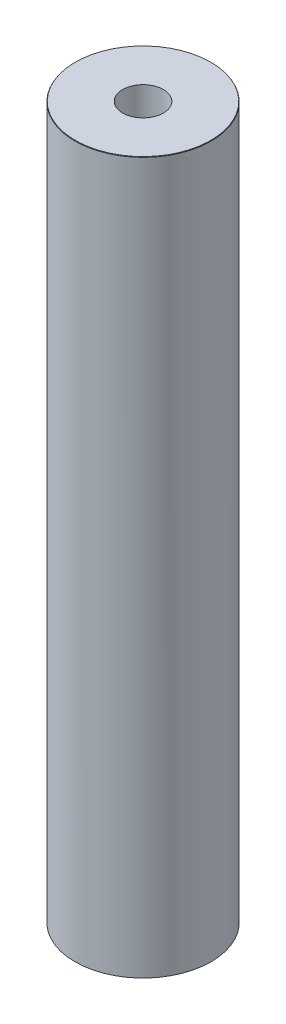
SolidWorks part; units mm, degrees
ref_plane "Front Plane" through (0, 0, 0) normal (0, 0, 1) x (1, 0, 0)
ref_plane "Top Plane" through (0, 0, 0) normal (0, 1, 0) x (1, 0, 0)
ref_plane "Right Plane" through (0, 0, 0) normal (1, 0, 0) x (0, 0, -1)
sketch "Sketch1" plane through (0, 0, 0) normal (0, 1, 0) x (1, 0, 0)
  circle A0 centre (0, 0) radius 55
  dimension "SHAFT_OD" = 110
extrude "Boss-Extrude1" add sketch "Sketch1" along normal blind 575.0269
sketch "Sketch2" plane through (0, 0, 0) normal (0, 1, 0) x (1, 0, 0)
  circle A0 centre (0, 0) radius 16.4651
  dimension "BORE_D" = 32.9301
extrude "Cut-Extrude1" cut sketch "Sketch2" along normal through all
chamfer "Chamfer1" distance 0.4078 angle 30 2 edges at (0, 575.0269, 55) (0, 0, 55) first distance on face at (0, 575.0269, 55) first distance on face at (0, 0, 16.4651)
